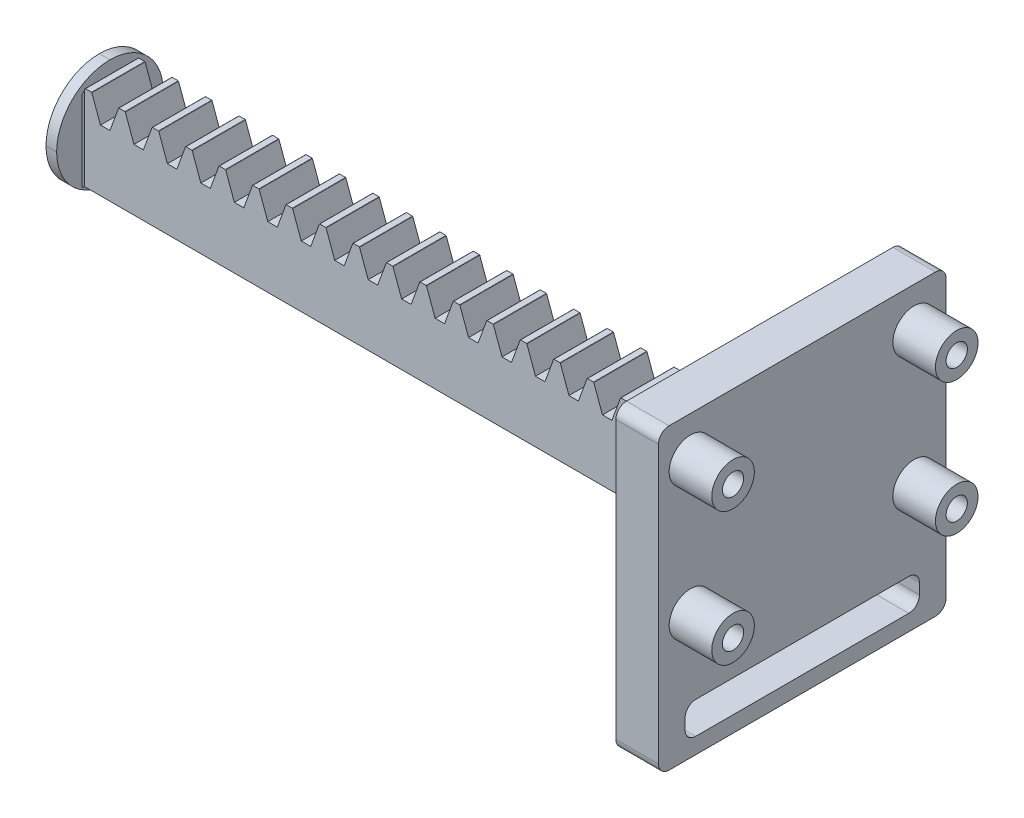
SolidWorks part; units mm, degrees
extrude "Blank" add sketch "BlankSke" against normal blind 5
sketch "BlankSke" plane through (0, 0, 0) normal (0, 0, 1) x (1, 0, 0)
  line L1 (0, 0) -> (125, 0)
  line L2 (0, 0) -> (0, 6)
  line L3 (0, 6) -> (125, 6)
  line L4 (125, 0) -> (125, 6)
  dimension "Length" = 125
ref_plane "Plane1" through (0, 0, 0) normal (0, 0, 1) x (1, 0, 0)
ref_plane "Plane2" through (0, 0, 0) normal (0, 1, 0) x (1, 0, 0)
ref_plane "Plane3" through (0, 0, 0) normal (1, 0, 0) x (0, 0, -1)
sketch "HoldingSke" plane through (0, 0, 0) normal (0, 1, 0) x (1, 0, 0)
  line L0 (0, 0) -> (0.1392, 0.9903)
  line L1 (-15, 0) -> (100, 0) construction
  line L2 (0, 0) -> (-2.1039, 2.3779)
  line L3 (0, 0) -> (-11.863, 4.5341)
  line L4 (0, 0) -> (6.5177, 5.6657)
  line L5 (0, 0) -> (-23.7986, -8.8762)
  line L6 (0, 0) -> (-10.5278, -7.1032)
  line L9 (-71.009, 38.7566) -> (46.4526, 81.5091)
  line L10 (-76.2, 3.3779) -> (-71.2, 3.3779)
  line L11 (0, 0) -> (-5, 0)
  line L12 (-76.2, 101.6) -> (-76.162, 101.6)
  line L13 (24.9733, 27.94) -> (52.9518, 28.4284)
  line L14 (24.9733, 27.94) -> (24.9743, 27.94)
  line L15 (24.9733, 27.94) -> (100.4006, 29.5858)
  circle A0 centre (0, 0) radius 19.05
  circle A1 centre (0, 0) radius 2.5
  circle A2 centre (0, 0) radius 12.7
  dimension "Num_teeth" = 41
  dimension "Width" = 5
  dimension "Length" = 125
  dimension "Pitch_height" = 5
sketch "TooCutSkeIll" plane through (0, 0, 0) normal (0, 0, 1) x (1, 0, 0)
  line L0 (-1.2538, 5.9737) -> (-0.5045, 3.9152)
  line L1 (-0.2687, 3.75) -> (0.2687, 3.75)
  line L2 (0.5045, 3.9152) -> (1.2538, 5.9737)
  line L3 (125, 6) -> (0, 6) construction
  line L4 (0, 0) -> (0, 64.897) construction
  line L5 (-13.208, 5) -> (12.954, 5) construction
  line L6 (0, 0) -> (125, 0) construction
  line L7 (0.8994, 5) -> (0.8994, 48.7463) construction
  line L8 (-0.8994, 5) -> (-0.8994, 48.7463) construction
  line L9 (1.2914, 6) -> (1.2914, 6.0254)
  line L10 (-1.2914, 6) -> (-1.2914, 6.0254)
  line L11 (-1.2914, 6.0254) -> (1.2914, 6.0254)
  arc A0 (0.2687, 3.75) -> (0.5045, 3.9152) centre (0.2687, 4.001) ccw
  arc A1 (-0.5045, 3.9152) -> (-0.2687, 3.75) centre (-0.2687, 4.001) ccw
  arc A2 (1.2914, 6) -> (1.2538, 5.9737) centre (1.2914, 5.96) ccw
  arc A3 (-1.2538, 5.9737) -> (-1.2914, 6) centre (-1.2914, 5.96) ccw
  dimension "Addendum_plus" = 1.0254
  dimension "Pitch_height" = 5
  dimension "Pressure_angle" = 20
  dimension "Gap_width" = 1.7988
  dimension "Dedendum" = 1.25
extrude "ToothCutIll" cut sketch "TooCutSkeIll" against normal through all
sketch "TooCutSkeSim" plane through (0, 0, 0) normal (0, 0, 1) x (1, 0, 0)
  line L0 (0.4444, 3.75) -> (-0.4444, 3.75)
  line L1 (1.2726, 6.0254) -> (0.4444, 3.75)
  line L2 (0, 17.4625) -> (0, 53.467) construction
  line L3 (1.2726, 6.0254) -> (-1.2726, 6.0254)
  line L6 (-1.2726, 6.0254) -> (-0.4444, 3.75)
  line L9 (-0.8994, 5) -> (0.8994, 5) construction
  line L10 (0, 0) -> (125, 0) construction
  line L11 (0.8994, 5) -> (0.8994, 53.467) construction
  line L12 (-0.8994, 5) -> (-0.8994, 53.467) construction
  dimension "Addendum_plus" = 1.0254
  dimension "Pitch_height" = 5
  dimension "Pressure_angle" = 20
  dimension "Gap_width" = 1.7988
  dimension "Dedendum" = 1.25
extrude "ToothCutSim" cut sketch "TooCutSkeSim" against normal through all
pattern_linear "TeethCuts" count 41 spacing 3.1416 along (1, 0, 0) of "ToothCutIll", "ToothCutSim"
sketch "Sketch1" plane through (0, 0, 0) normal (0, 0, 1) x (1, 0, 0)
  line L0 (125, 0) -> (125, 4.3524) construction
  line L1 (0, 0) -> (125, 0)
  line L2 (0, 0) -> (0, -2)
  line L3 (0, -2) -> (125, -2)
  line L4 (125, 0) -> (125, -2)
  dimension "D1" = 2
extrude "Boss-Extrude1" add sketch "Sketch1" against normal blind 5
sketch "Sketch2" plane through (0, 0, -5) normal (0, 0, -1) x (-1, 0, 0)
  line L0 (-62.5, -2) -> (-62.5, 18.8437) construction
  line L1 (-125, -2) -> (-92.5, -2)
  line L2 (-125, -2) -> (-125, 8.9347)
  line L3 (-125, 8.9347) -> (-92.5, 8.9347)
  line L4 (-92.5, -2) -> (-92.5, 8.9347)
  line L5 (0, -2) -> (-32.5, -2)
  line L6 (0, -2) -> (0, 10.3795)
  line L7 (0, 10.3795) -> (-32.5, 10.3795)
  line L8 (-32.5, -2) -> (-32.5, 10.3795)
  line L9 (0, -2) -> (-125, -2) construction
  dimension "D1" = 30
  dimension "D2" = 30
extrude "Cut-Extrude1" cut sketch "Sketch2" against normal blind 42
sketch "Sketch3" plane through (32.5, 0, 0) normal (-1, 0, 0) x (0, 0, 1)
  line L0 (-2.5, -2) -> (-2.5, 6) construction
  line L1 (-5, -2) -> (0, -2) construction
  line L4 (-7.5, -3) -> (2.5, -3)
  line L5 (-7.5, -3) -> (-7.5, 7)
  line L6 (-7.5, 7) -> (2.5, 7)
  line L7 (2.5, -3) -> (2.5, 7)
  line L8 (-7.5, -3) -> (2.5, 7) construction
  line L9 (-7.5, 7) -> (2.5, -3) construction
  point P6 (-2.5, 2)
  dimension "D1" = 10
  dimension "D2" = 10
extrude "Boss-Extrude2" add sketch "Sketch3" along normal blind 1
sketch "Sketch4" plane through (92.5, 0, 0) normal (1, 0, 0) x (0, 0, -1)
  line L0 (2.5, -2) -> (2.5, 6) construction
  line L1 (0, -2) -> (5, -2) construction
  line L2 (5, 6) -> (0, 6) construction
  line L4 (7.5, -3) -> (-2.5, -3)
  line L5 (7.5, -3) -> (7.5, 7)
  line L6 (7.5, 7) -> (-2.5, 7)
  line L7 (-2.5, -3) -> (-2.5, 7)
  line L8 (7.5, -3) -> (-2.5, 7) construction
  line L9 (7.5, 7) -> (-2.5, -3) construction
  point P6 (2.5, 2)
extrude "Boss-Extrude3" add sketch "Sketch4" along normal blind 1
sketch "Sketch5" plane through (93.5, 0, 0) normal (1, 0, 0) x (0, 0, -1)
  line L0 (-2.5, 2) -> (7.5, 2) construction
  line L1 (-2.5, 7) -> (-2.5, -3) construction
  line L2 (7.5, -3) -> (7.5, 7) construction
  circle A0 centre (2.5, 2) radius 7.5
  dimension "D1" = 15
extrude "Boss-Extrude4" [suppressed] add sketch "Sketch5" along normal blind 11
sketch "Sketch6" [suppressed] plane through (96.5, 0, 0) normal (1, 0, 0) x (0, 0, -1)
  circle A0 centre (2.5, 2) radius 3.85
  dimension "D1" = 7.7
extrude "Cut-Extrude2" [suppressed] cut sketch "Sketch6" against normal blind 8
sketch "Sketch7" [suppressed] plane through (0, 0, 0) normal (0, 0, 1) x (1, 0, 0)
  line L0 (96.5, 2) -> (91.5, 2) construction
  line L1 (96.5, -5.5) -> (96.5, 9.5) construction
  circle A0 centre (91.5, 2) radius 1.8
  dimension "D1" = 3.6
  dimension "D2" = 5
extrude "Cut-Extrude3" [suppressed] cut sketch "Sketch7" against normal blind 15
chamfer "Chamfer1" distance 0.1 angle 45 6 edges at (32.5, 1.7537, 0) (32.5, -2, -2.5) (32.5, 1.7537, -5) (92.5, 2, -5) (92.5, -2, -2.5) (92.5, 2, 0)
chamfer "Chamfer2" [suppressed] distance 1 angle 45
fillet "Fillet1" radius 5 8 edges at (32, -3, 2.5) (32, -3, -7.5) (32, 7, -7.5) (32, 7, 2.5) (93, 7, 2.5) (93, 7, -7.5) (93, -3, 2.5) (93, -3, -7.5)
sketch "Sketch8" plane through (93.5, 0, 0) normal (1, 0, 0) x (0, 0, -1)
  line L0 (2.5, -3) -> (2.5, 2) construction
  line L2 (-11, -12) -> (16, -12)
  line L3 (-11, -12) -> (-11, 16)
  line L4 (-11, 16) -> (16, 16)
  line L5 (16, -12) -> (16, 16)
  line L6 (-11, -12) -> (16, 16) construction
  line L7 (-11, 16) -> (16, -12) construction
  dimension "D1" = 28
  dimension "D2" = 27
extrude "Boss-Extrude5" add sketch "Sketch8" along normal blind 4
sketch "Sketch9" plane through (93.5, 0, 0) normal (-1, 0, 0) x (0, 0, 1)
  line L0 (-2.5, -3) -> (-2.5, 7) construction
  line L1 (-16, 16) -> (11, 16) construction
  line L2 (-13, -0.25) -> (8, -0.25) construction
  line L3 (-13, -0.25) -> (-13, 12.25) construction
  line L4 (-13, 12.25) -> (8, 12.25) construction
  line L5 (8, -0.25) -> (8, 12.25) construction
  line L6 (-13, -0.25) -> (8, 12.25) construction
  line L7 (-13, 12.25) -> (8, -0.25) construction
  circle A0 centre (-13, 12.25) radius 1
  circle A1 centre (8, 12.25) radius 1
  circle A2 centre (8, -0.25) radius 1
  circle A3 centre (-13, -0.25) radius 1
  point P4 (-2.5, 6)
  point P13 (0, 0)
  point P14 (-2.5, 5.7674)
  dimension "D1" = 2
  dimension "D2" = 2
  dimension "D3" = 2
  dimension "D4" = 2
  dimension "D5" = 12.5
  dimension "D6" = 21
  dimension "D7" = 10
extrude "Cut-Extrude4" cut sketch "Sketch9" against normal blind 11
fillet "Fillet2" radius 1 4 edges at (95.5, -12, -16) (95.5, -12, 11) (95.5, 16, -16) (95.5, 16, 11)
sketch "Sketch10" plane through (97.5, 0, 0) normal (1, 0, 0) x (0, 0, -1)
  line L0 (2.5, 16) -> (2.5, -9) construction
  line L1 (15, 16) -> (-10, 16) construction
  line L3 (-8.5, -7.5) -> (13.5, -7.5)
  line L4 (-8.5, -7.5) -> (-8.5, -10.5)
  line L5 (-8.5, -10.5) -> (13.5, -10.5)
  line L6 (13.5, -7.5) -> (13.5, -10.5)
  line L7 (-8.5, -7.5) -> (13.5, -10.5) construction
  line L8 (-8.5, -10.5) -> (13.5, -7.5) construction
  dimension "D1" = 25
  dimension "D2" = 3
  dimension "D3" = 22
extrude "Cut-Extrude5" cut sketch "Sketch10" against normal blind 10
fillet "Fillet3" radius 1 4 edges at (95.5, -7.5, -13.5) (95.5, -10.5, -13.5) (95.5, -10.5, 8.5) (95.5, -7.5, 8.5)
sketch "Sketch11" plane through (97.5, 0, 0) normal (1, 0, 0) x (0, 0, -1)
  line L0 (2.5, 16) -> (2.5, -2.0265) construction
  line L1 (15, 16) -> (-10, 16) construction
  circle A0 centre (-8, 12.25) radius 1
  circle A1 centre (-8, 12.25) radius 2
  circle A2 centre (-8, -0.25) radius 1
  circle A3 centre (-8, -0.25) radius 2
  circle A4 centre (13, -0.25) radius 2
  circle A5 centre (13, -0.25) radius 1
  circle A6 centre (13, 12.25) radius 2
  circle A7 centre (13, 12.25) radius 1
  dimension "D1" = 4
  dimension "D2" = 2
  dimension "D3" = 2
  dimension "D4" = 4
extrude "Boss-Extrude6" add sketch "Sketch11" along normal blind 4
equation "' \"Module@HoldingSke\" = 6.35"
equation "' \"Num_teeth@HoldingSke\" = 12"
equation "' \"Ap@HoldingSke\" =  20"
equation "' \"Ap@HoldingSke\" = 20"
equation "' \"Width@HoldingSke\" = 0.25 * 25.4"
equation "' \"Show_teeth@HoldingSke\" = 500"
equation "' \"Backlash@HoldingSke\" = 0.009 * 25.4"
equation "' \"Addendum_fac@HoldingSke\" = 1.0"
equation "' \"Dedendum_fac@HoldingSke\" = 1.25"
equation "' \"Dedendum_add@HoldingSke\" = 0.00005 * 25.4"
equation "' \"Clearance_fac@HoldingSke\" = 0.25"
equation "' \"Pitch_height@HoldingSke\" = 1 * 25.4"
equation "' \"Length@HoldingSke\" = 4.71 * 25.4"
equation "\"Pitch@HoldingSke\" = 1 / \"Module@HoldingSke\""
equation "\"MPH@HoldingSke\" = \"Dedendum_fac@HoldingSke\" / \"Pitch@HoldingSke\" + 2 * \"Dedendum_add@HoldingSke\" + 0.002 * 25.4"
equation "\"MPH@HoldingSke\" = ((sgn( \"MPH@HoldingSke\" - \"Pitch_height@HoldingSke\")+1)*( \"MPH@HoldingSke\" - \"Pitch_height@HoldingSke\"))/2 + \"Pitch_height@HoldingSke\""
equation "\"Blank_height@BlankSke\" = \"Pitch_height@HoldingSke\" + \"Addendum_fac@HoldingSke\"  / \"Pitch@HoldingSke\" "
equation "\"Length@BlankSke\" =  \"Length@HoldingSke\""
equation "\"Face_width@Blank\" = \"Width@HoldingSke\""
equation "\"Pressure_angle@TooCutSkeIll\" = \"Ap@HoldingSke\""
equation "\"Addendum_plus@TooCutSkeIll\" =  \"Addendum_fac@HoldingSke\"  / \"Pitch@HoldingSke\" + 0.001 *25.4"
equation "\"Dedendum@TooCutSkeIll\" = \"Dedendum_fac@HoldingSke\"  / \"Pitch@HoldingSke\""
equation "\"Pitch_height@TooCutSkeIll\" =  \"MPH@HoldingSke\""
equation "\"Gap_width@TooCutSkeIll\" = 3.14159265 / 2 / \"Pitch@HoldingSke\" + 6 * \"Backlash@HoldingSke\""
equation "\"Pressure_angle@TooCutSkeSim\" = \"Ap@HoldingSke\""
equation "\"Addendum_plus@TooCutSkeSim\" =  \"Addendum_fac@HoldingSke\"  / \"Pitch@HoldingSke\" + 0.001 * 25.4"
equation "\"Dedendum@TooCutSkeSim\" = \"Dedendum_fac@HoldingSke\"  / \"Pitch@HoldingSke\""
equation "\"Pitch_height@TooCutSkeSim\" =  \"MPH@HoldingSke\""
equation "\"Gap_width@TooCutSkeSim\" = 3.14159265 / 2 / \"Pitch@HoldingSke\" + 6 * \"Backlash@HoldingSke\""
equation "\"Root_fillet@TooCutSkeIll\" = \"Clearance_fac@HoldingSke\" / \"Pitch@HoldingSke\" + \"Dedendum_add@HoldingSke\""
equation "\"Break_rad@TooCutSkeIll\" = 0.02 / \"Pitch@HoldingSke\" * 2"
equation "\"Linear_pitch@TeethCuts\" = 3.14159265 / \"Pitch@HoldingSke\""
equation "\"Num_teeth@HoldingSke\" = int( ( \"Length@HoldingSke\" + 0 ) / (3.14159265 / \"Pitch@HoldingSke\")) + 0.9999  + 1"
equation " \"Num_teeth@TeethCuts\" = int( \"Show_teeth@HoldingSke\" ) + 1"
equation " \"Num_teeth@TeethCuts\" = ((sgn( \"Num_teeth@TeethCuts\" - \"Num_teeth@HoldingSke\" )-1)*( \"Num_teeth@TeethCuts\" - \"Num_teeth@HoldingSke\" ))/-2+ \"Num_teeth@HoldingSke\""
equation " \"Num_teeth@TeethCuts\" = ((sgn( \"Num_teeth@TeethCuts\" - 2.0)+1)*( \"Num_teeth@TeethCuts\" - 2.0))/2 +2.0"
